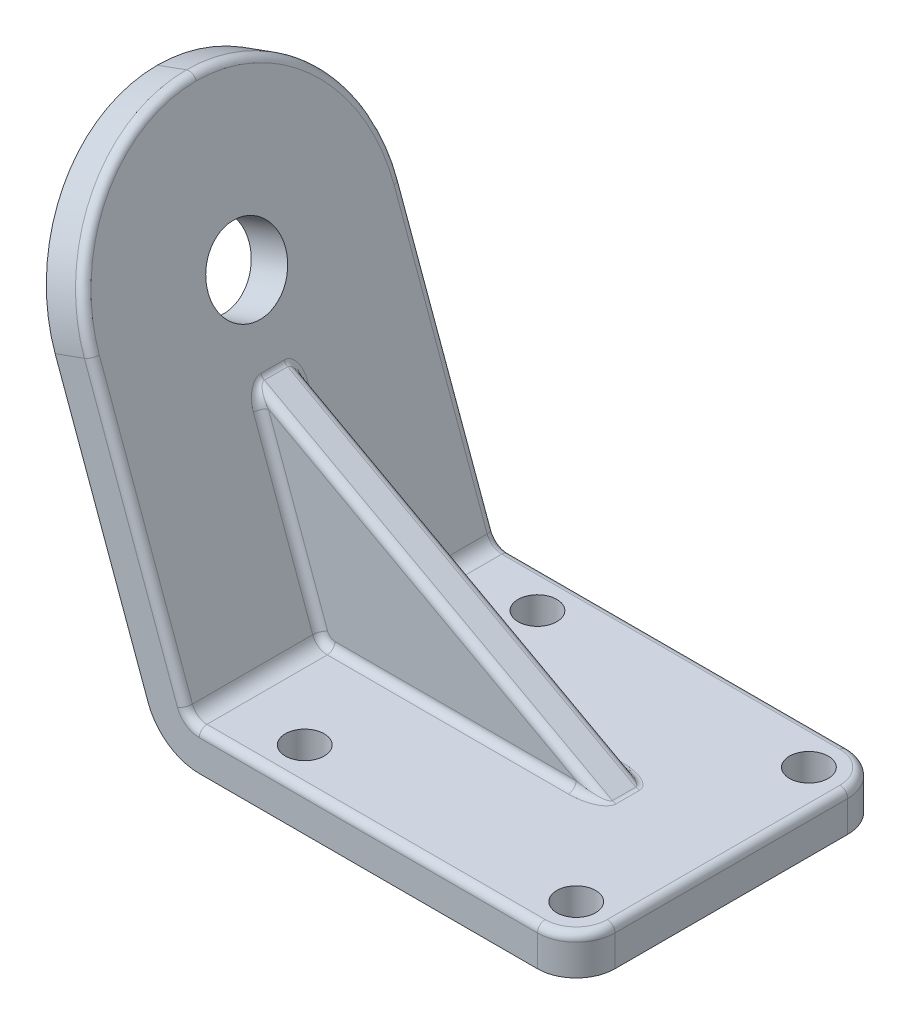
SolidWorks part; units mm, degrees
ref_plane "前基準面" through (0, 0, 0) normal (0, 0, 1) x (1, 0, 0)
ref_plane "上基準面" through (0, 0, 0) normal (0, 1, 0) x (1, 0, 0)
ref_plane "右基準面" through (0, 0, 0) normal (1, 0, 0) x (0, 0, -1)
sketch "草圖1" plane through (0, 0, 0) normal (0, 0, 1) x (1, 0, 0)
  line L0 (0, 0) -> (53.501, 0)
  line L1 (53.501, 0) -> (53.501, 5)
  line L2 (53.501, 5) -> (3.501, 5)
  line L3 (3.501, 5) -> (-15.8227, 58.0917)
  line L4 (-15.8227, 58.0917) -> (-20.5212, 56.3816)
  line L5 (-20.5212, 56.3816) -> (0, 0)
  dimension "D1" = 50
  dimension "D2" = 60
  dimension "D3" = 5
  dimension "D4" = 110
  dimension "D5" = 5
extrude "填料-伸長1" add sketch "草圖1" along normal mid plane 40
fillet "圓角1" radius 2 1 edges at (3.501, 5, 0)
fillet "圓角2" radius 7 1 edges at (0, 0, 0)
fillet "圓角11" radius 20 2 edges at (-18.172, 57.2366, 20) (-18.172, 57.2366, -20)
sketch "草圖2" plane through (0, 0, 0) normal (0, 0, 1) x (1, 0, 0)
  line L0 (39.9015, 5) -> (-5.5284, 29.8083)
  line L1 (53.501, 5) -> (4.9015, 5) construction
  line L2 (3.0221, 6.316) -> (-8.9823, 39.2978) construction
  line L9 (3.0221, 6.316) -> (-8.9823, 39.2978)
  line L10 (-8.9823, 39.2978) -> (-13.6808, 37.5877)
  line L11 (-13.6808, 37.5877) -> (-1.6764, 4.6059)
  line L12 (4.9015, 0) -> (53.501, 0)
  line L13 (53.501, 0) -> (53.501, 5)
  line L14 (53.501, 5) -> (4.9015, 5)
  line L15 (3.0221, 6.316) -> (-5.5284, 29.8083)
  line L20 (39.9015, 5) -> (4.9015, 5)
  arc A2 (-1.6764, 4.6059) -> (4.9015, 0) centre (4.9015, 7) ccw
  arc A3 (3.0221, 6.316) -> (4.9015, 5) centre (4.9015, 7) ccw
  arc A5 (3.0221, 6.316) -> (4.9015, 5) centre (4.9015, 7) ccw
  dimension "D1" = 25
  dimension "D2" = 35
  dimension "D3" = 0
extrude "填料-伸長2" add sketch "草圖2" along normal mid plane 5
fillet "圓角12" radius 1 9 edges at (-13.8192, 52.5871, -14.1421) (-2.9801, 22.8069, -20) (3.7543, 5.3617, -20) (29.2012, 5, -20) (53.501, 5, 0) (29.2012, 5, 20) (3.7543, 5.3617, 20) (-2.9801, 22.8069, 20) (-13.8192, 52.5871, 14.1421)
fillet "圓角14" radius 1 10 edges at (39.9015, 5, 0) (-5.5284, 29.8083, 0) (22.4015, 5, -2.5) (22.4015, 5, 2.5) (3.7543, 5.3617, 2.5) (3.7543, 5.3617, -2.5) (-1.2532, 18.0621, -2.5) (-1.2532, 18.0621, 2.5) (17.1865, 17.4041, -2.5) (17.1865, 17.4041, 2.5)
sketch "草圖3" plane through (4.6985, 1.7101, 0) normal (0.9397, 0.342, 0) x (0, 0, -1)
  circle A0 centre (0, 40) radius 5
  dimension "D3" = 10
  dimension "D1" = 20
  dimension "D2" = 20
extrude "除料-伸長1" cut sketch "草圖3" against normal through all
fillet "圓角15" radius 5 4 edges at (53.2081, 4.7071, -19.7071) (53.2081, 4.7071, 19.7071) (53.501, 2, 20) (53.501, 2, -20)
sketch "草圖4" plane through (0, 5, 0) normal (0, 1, 0) x (1, 0, 0)
  line L0 (4.9015, 20) -> (48.501, 20) construction
  line L1 (53.501, 15) -> (53.501, -15) construction
  circle A0 centre (48.501, 15) radius 2.5
  dimension "D3" = 5
  dimension "D1" = 5
  dimension "D2" = 5
extrude "除料-伸長2" cut sketch "草圖4" against normal through all
pattern_linear "直線複製排列2" count 2 spacing 35 along (-1, 0, 0) count 2 spacing 30 along (0, 0, 1) of "除料-伸長2"
